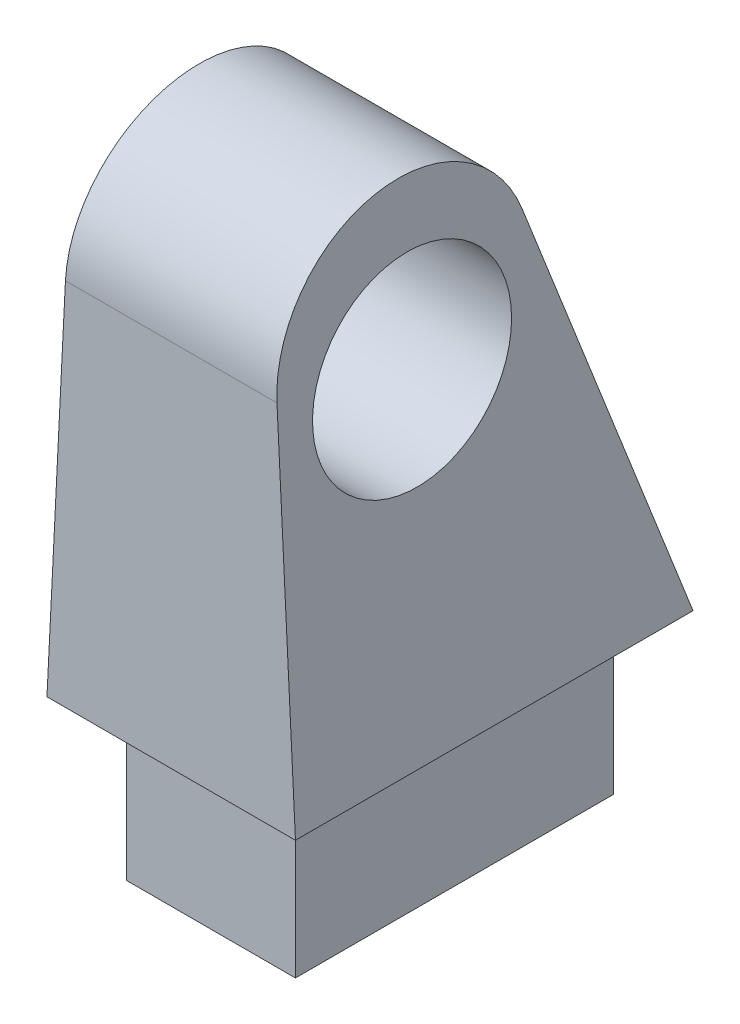
SolidWorks part; units mm, degrees
ref_plane "Front Plane" through (0, 0, 0) normal (0, 0, 1) x (1, 0, 0)
ref_plane "Top Plane" through (0, 0, 0) normal (0, 1, 0) x (1, 0, 0)
ref_plane "Right Plane" through (0, 0, 0) normal (1, 0, 0) x (0, 0, -1)
sketch "Sketch1" plane through (0, 0, 0) normal (1, 0, 0) x (0, 0, -1)
  line L0 (1.547, 13.1962) -> (6.35, 0)
  line L1 (6.35, 0) -> (-6.35, 0)
  line L2 (-6.35, 0) -> (-6.35, 11.8037)
  line L3 (-10.0809, 15.875) -> (13.4038, 15.875) construction
  arc A3 (1.547, 13.1962) -> (-6.35, 11.8037) centre (-2.2787, 11.8037) ccw
  circle A4 centre (-2.0941, 10.6275) radius 3.175
  point P8 (0, 0)
  point P9 (-1.928, 10.8566)
  point P12 (-2.0941, 10.6275)
  dimension "D1" = 15.875
  dimension "D3" = 70
  dimension "D4" = 6.35
  dimension "D2" = 12.7
extrude "Boss-Extrude1" add sketch "Sketch1" along normal blind 7.9375
sketch "Sketch2" plane through (0, 0, 6.35) normal (0, 0, 1) x (1, 0, 0)
  line L0 (0, 0) -> (7.9375, 0)
  line L1 (7.9375, 0) -> (7.1437, 15.875)
  line L2 (7.9375, 15.875) -> (0, 15.875) construction
  line L3 (7.1437, 15.875) -> (0.7938, 15.875)
  line L4 (0.7938, 15.875) -> (0, 0)
  point P8 (3.9688, 15.875)
  point P9 (3.9688, 0)
  dimension "D1" = 6.35
extrude "Cut-Extrude1" cut sketch "Sketch2" against normal through all flip side to cut
sketch "Sketch3" plane through (0, 0, 0) normal (0, -1, 0) x (1, 0, 0)
  line L0 (7.9375, 6.35) -> (0, 6.35) construction
  line L1 (1.27, -5.08) -> (6.6675, -5.08)
  line L2 (1.27, -5.08) -> (1.27, 5.08)
  line L3 (1.27, 5.08) -> (6.6675, 5.08)
  line L4 (6.6675, -5.08) -> (6.6675, 5.08)
  line L5 (1.27, -5.08) -> (6.6675, 5.08) construction
  line L6 (1.27, 5.08) -> (6.6675, -5.08) construction
  line L7 (7.9375, 6.35) -> (7.9375, -6.35) construction
  point P0 (3.9688, 0)
  point P5 (0, 0)
  point P11 (0, 0)
  point P12 (3.9688, 6.35)
  dimension "D1" = 1.27
  dimension "D2" = 1.27
extrude "Boss-Extrude2" add sketch "Sketch3" along normal blind 5.08
sketch "Sketch4" plane through (0, 0, 0) normal (0, -1, 0) x (1, 0, 0)
  line L0 (0, 0) -> (7.9375, 0)
  line L1 (0, 6.35) -> (0, -6.35) construction
  line L2 (7.9375, 6.35) -> (7.9375, -6.35) construction
  point P6 (3.9688, 0)
ref_plane "Plane1" through (3.9688, 0, 0) normal (-1, 0, 0) x (0, 0, 1)
equation "\"D1@Boss-Extrude1\"=5/16in"
